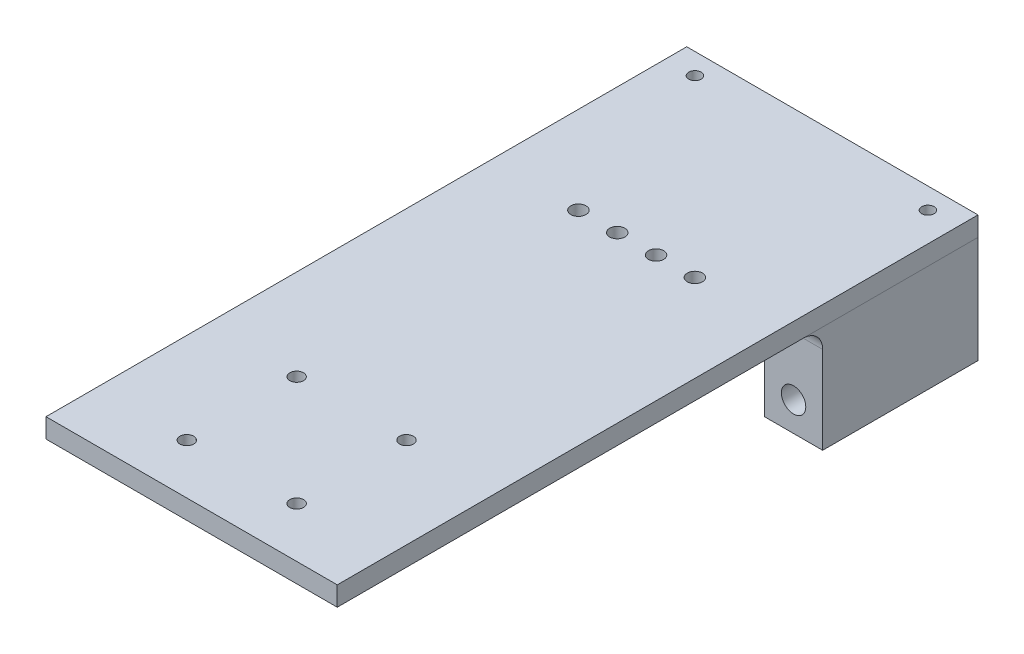
SolidWorks part; units mm, degrees
ref_plane "Front Plane" through (0, 0, 0) normal (0, 0, 1) x (1, 0, 0)
ref_plane "Top Plane" through (0, 0, 0) normal (0, 1, 0) x (1, 0, 0)
ref_plane "Right Plane" through (0, 0, 0) normal (1, 0, 0) x (0, 0, -1)
sketch "Sketch1" plane through (0, 0, 0) normal (0, 0, 1) x (1, 0, 0)
  line L0 (-47.625, 0) -> (47.625, 0)
  line L1 (-47.625, 0) -> (-47.625, -41.275)
  line L2 (-47.625, -41.275) -> (-28.575, -41.275)
  line L3 (-28.575, -41.275) -> (-28.575, -12.7)
  line L5 (47.625, 0) -> (47.625, -41.275)
  line L6 (47.625, -41.275) -> (28.575, -41.275)
  line L7 (28.575, -41.275) -> (28.575, -12.7)
  line L9 (-28.575, -12.7) -> (28.575, -12.7)
  point P4 (0, 0)
  dimension "D1" = 95.25
  dimension "D2" = 28.575
  dimension "D3" = 19.05
  dimension "D4" = 19.05
  dimension "D5" = 41.275
extrude "Boss-Extrude1" add sketch "Sketch1" along normal mid plane 50.8
fillet "Fillet1" radius 6.35 2 edges at (28.575, -12.7, 0) (-28.575, -12.7, 0)
sketch "Sketch2" plane through (0, 0, 25.4) normal (0, 0, 1) x (1, 0, 0)
  line L0 (-47.625, -41.275) -> (-28.575, -41.275) construction
  circle A0 centre (-38.1, -31.75) radius 4.0005
  circle A1 centre (38.1, -31.75) radius 4
  dimension "D3" = 8.001
  dimension "D5" = 8
  dimension "D1" = 38.1
  dimension "D2" = 38.1
  dimension "D4" = 9.525
extrude "Cut-Extrude1" cut sketch "Sketch2" against normal up to surface (50.8 mm away) up to face at (0, -22.597, -25.4)
sketch "Sketch3" plane through (0, 0, -25.4) normal (0, 0, -1) x (-1, 0, 0)
  line L0 (47.625, 0) -> (47.625, -41.275) construction
  line L1 (-47.625, 0) -> (47.625, 0)
  line L2 (-47.625, 0) -> (-47.625, -6.35)
  line L3 (-47.625, -6.35) -> (47.625, -6.35)
  line L4 (47.625, 0) -> (47.625, -6.35)
  dimension "D1" = 6.35
extrude "Boss-Extrude2" [suppressed] add sketch "Sketch3" along normal blind 25.4
sketch "Sketch4" plane through (0, 0, 25.4) normal (0, 0, 1) x (1, 0, 0)
  line L0 (47.625, -41.275) -> (47.625, 0) construction
  line L1 (-47.625, 0) -> (47.625, 0)
  line L2 (-47.625, 0) -> (-47.625, -6.35)
  line L3 (-47.625, -6.35) -> (47.625, -6.35)
  line L4 (47.625, 0) -> (47.625, -6.35)
  dimension "D1" = 6.35
extrude "Boss-Extrude3" add sketch "Sketch4" along normal blind 158.75
sketch "Sketch5" plane through (0, 0, 0) normal (0, 1, 0) x (1, 0, 0)
  line L1 (47.625, 25.4) -> (-47.625, 25.4) construction
  circle A0 centre (-38.1, 18.542) radius 2.0193
  dimension "D1" = 4.0386
  dimension "D2" = 38.1
  dimension "D3" = 6.858
extrude "Cut-Extrude2" cut sketch "Sketch5" against normal blind 12.7
mirror "Mirror1" about plane through (0, 0, 0) normal (1, 0, 0) of "Cut-Extrude2"
fillet "Fillet2" radius 6.35 1 edges at (0, -6.35, 25.4)
sketch "Sketch6" plane through (0, 0, 0) normal (0, 1, 0) x (1, 0, 0)
  line L0 (0, 0) -> (0, -226.7708) construction
  line L1 (32.385, -176.9603) -> (-32.385, -176.9603) construction
  line L3 (47.625, -184.15) -> (-47.625, -184.15) construction
  circle A0 centre (-17.9605, -167.767) radius 2.2479
  circle A1 centre (-17.9605, -131.846) radius 2.2479
  circle A2 centre (17.9605, -167.767) radius 2.2479
  circle A3 centre (17.9605, -131.846) radius 2.2479
  point P14 (0, -176.9603)
  dimension "D1" = 4.4958
  dimension "D2" = 35.921
  dimension "D3" = 35.921
  dimension "D4" = 64.77
  dimension "D5" = 17.9605
  dimension "D6" = 16.383
extrude "Cut-Extrude3" cut sketch "Sketch6" against normal up to surface (6.35 mm away) up to face at (0, -6.35, 107.95)
sketch "Sketch10" plane through (0, 0, 0) normal (0, 1, 0) x (1, 0, 0)
  line L0 (0, 0) -> (0, -57.4301) construction
  circle A0 centre (38.1, 18.542) radius 2.0193 construction
  circle A1 centre (-38.1, 18.542) radius 2.0193 construction
  circle A2 centre (38.1, 18.542) radius 2.0193 construction
  circle A3 centre (-38.1, 18.542) radius 2.0193 construction
  circle A4 centre (-6.35, -38.608) radius 2.4892
  circle A5 centre (-19.05, -38.608) radius 2.4892
  dimension "D4" = 4.9784
  dimension "D1" = 57.15
  dimension "D2" = 6.35
  dimension "D3" = 19.05
extrude "Cut-Extrude4" cut sketch "Sketch10" against normal through all
mirror "Mirror2" about plane through (0, 0, 0) normal (1, 0, 0) of "Cut-Extrude4"
sketch "Sketch11" [suppressed] plane through (0, -41.275, 0) normal (0, -1, 0) x (1, 0, 0)
  line L1 (47.625, -25.4) -> (-47.625, -25.4)
  line L2 (47.625, -25.4) -> (47.625, 31.75)
  line L3 (47.625, 31.75) -> (-47.625, 31.75)
  line L4 (-47.625, -25.4) -> (-47.625, 31.75)
  point P5 (0, 0)
  dimension "D1" = 95.25
  dimension "D2" = 31.75
extrude "Cut-Extrude5" [suppressed] cut sketch "Sketch11" against normal up to surface (34.925 mm away) up to face at (6.35, -6.35, 41.0972)
split "Split1" bodies to split 110 resulting bodies 112 113 split by face at (6.35, -6.35, 41.0972)
